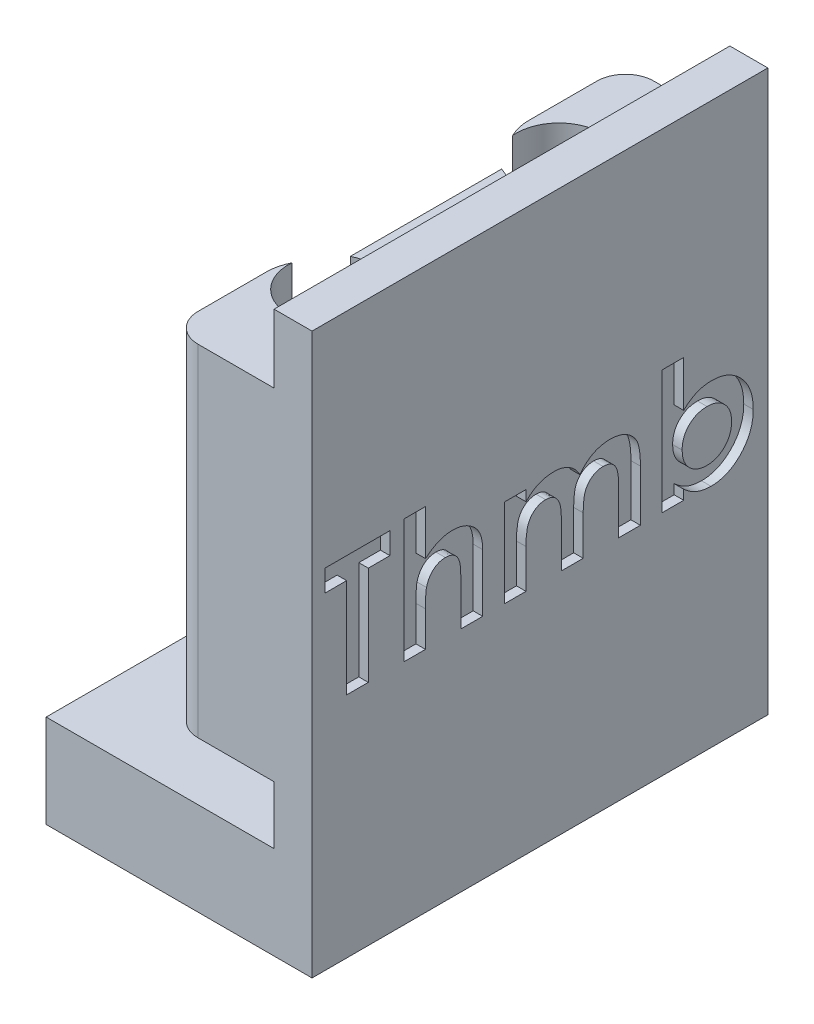
SolidWorks part; units mm, degrees
ref_plane "Front" through (0, 0, 0) normal (0, 0, 1) x (1, 0, 0)
ref_plane "Top" through (0, 0, 0) normal (0, 1, 0) x (1, 0, 0)
ref_plane "Right" through (0, 0, 0) normal (1, 0, 0) x (0, 0, -1)
sketch "Sketch1" plane through (0, 0, 0) normal (0, 1, 0) x (1, 0, 0)
  line L5 (-6, -12) -> (6, -12)
  line L6 (-6, -12) -> (-6, 12)
  line L7 (-6, 12) -> (6, 12)
  line L8 (6, -12) -> (6, 12)
  line L9 (-6, -12) -> (6, 12) construction
  line L10 (-6, 12) -> (6, -12) construction
  point P0 (0, 0)
  dimension "D1" = 12
  dimension "D2" = 24
extrude "Boss-Extrude1" add sketch "Sketch1" along normal blind 4.9
sketch "Sketch2" plane through (0, 0, 0) normal (0, 1, 0) x (1, 0, 0)
  line L0 (6, 12) -> (-6, 12) construction
  line L1 (6, -12) -> (8, -12)
  line L2 (6, -12) -> (6, 12)
  line L3 (6, 12) -> (8, 12)
  line L4 (8, -12) -> (8, 12)
  dimension "D1" = 2
extrude "Boss-Extrude2" add sketch "Sketch2" along normal blind 29.5
sketch "Sketch4" plane through (0, 4.9, 0) normal (0, 1, 0) x (1, 0, 0)
  line L1 (6, -12) -> (0.5, -12)
  line L2 (6, -12) -> (6, 12)
  line L3 (6, 12) -> (0.5, 12)
  line L4 (0.5, -12) -> (0.5, 12)
  line L5 (6, 12) -> (-6, 12) construction
  dimension "D1" = 5.5
extrude "Boss-Extrude4" add sketch "Sketch4" along normal blind 17.95 from offset 3.05
sketch "Sketch5" plane through (0.5, 0, 0) normal (-1, 0, 0) x (0, 0, 1)
  line L0 (-12, 25.9) -> (12, 25.9) construction
  line L1 (-4.625, 25.9) -> (4.625, 25.9)
  line L2 (-4.625, 25.9) -> (-4.625, 7.95)
  line L3 (-4.625, 7.95) -> (4.625, 7.95)
  line L4 (4.625, 25.9) -> (4.625, 7.95)
  line L5 (-12, 7.95) -> (12, 7.95) construction
  line L8 (4.625, 25.9) -> (12, 25.9) construction
  line L9 (-4.625, 25.9) -> (-12, 25.9) construction
  dimension "D1" = 9.25
extrude "Cut-Extrude1" cut sketch "Sketch5" against normal blind 1.5
fillet "Fillet1" radius 2.5 2 edges at (0.5, 16.925, 4.625) (0.5, 16.925, -4.625)
sketch "Sketch6" plane through (0, 25.9, 0) normal (0, 1, 0) x (1, 0, 0)
  line L1 (6, -12) -> (6, 12) construction
  line L3 (3, -12) -> (3, -6) construction
  line L4 (0.5, -12) -> (6, -12) construction
  line L5 (3, -6) -> (6, -6) construction
  line L7 (3, 12) -> (3, 6) construction
  line L9 (3, 6) -> (6, 6) construction
  line L10 (6, 12) -> (0.5, 12) construction
  circle A0 centre (3, -6) radius 2.25
  circle A4 centre (3, 6) radius 2.25
  dimension "D3" = 4.5
  dimension "D8" = 4.5
  dimension "D1" = 6
  dimension "D2" = 3
  dimension "D6" = 6
  dimension "D7" = 3
extrude "Cut-Extrude2" cut sketch "Sketch6" against normal through all
fillet "Fillet2" radius 1.5 2 edges at (0.5, 16.925, -12) (0.5, 16.925, 12)
sketch "Sketch7" plane through (8, 0, 0) normal (1, 0, 0) x (0, 0, -1)
  line L0 (-12, 29.5) -> (-12, 0) construction
  line L2 (-12, 0) -> (12, 0) construction
  text T0 "<b>Thmb</b>"
  dimension "D1" = 0.6
  dimension "D2" = 12
extrude "Cut-Extrude3" cut sketch "Sketch7" against normal blind 0.5
